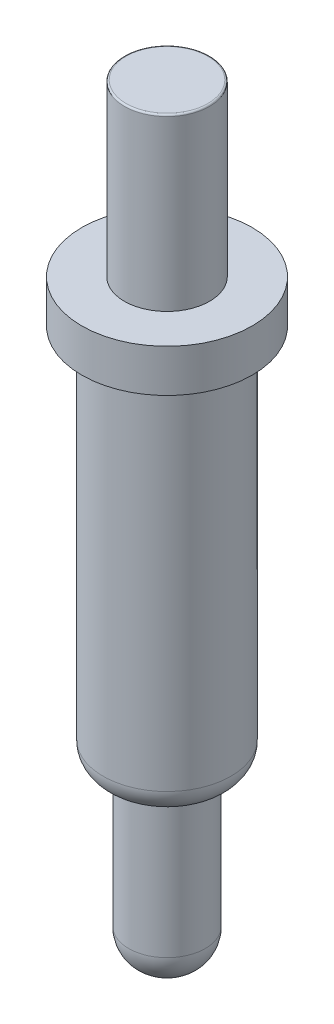
SolidWorks part; units mm, degrees
ref_plane "Front Plane" through (0, 0, 0) normal (0, 0, 1) x (1, 0, 0)
ref_plane "Top Plane" through (0, 0, 0) normal (0, 1, 0) x (1, 0, 0)
ref_plane "Right Plane" through (0, 0, 0) normal (1, 0, 0) x (0, 0, -1)
sketch "Sketch1" plane through (0, 0, 0) normal (0, 1, 0) x (1, 0, 0)
  circle A0 centre (0, 0) radius 1
  dimension "D1" = 2
extrude "Boss-Extrude1" add sketch "Sketch1" along normal blind 0.5
sketch "Sketch2" plane through (0, 0.5, 0) normal (0, 1, 0) x (1, 0, 0)
  circle A0 centre (0, 0) radius 0.5
  dimension "D1" = 1
extrude "Boss-Extrude2" add sketch "Sketch2" along normal blind 2
sketch "Sketch3" plane through (0, 0, 0) normal (0, -1, 0) x (1, 0, 0)
  circle A0 centre (0, 0) radius 0.75
  dimension "D1" = 1.5
extrude "Boss-Extrude3" add sketch "Sketch3" along normal blind 4.5
sketch "Sketch4" plane through (0, -4.5, 0) normal (0, -1, 0) x (1, 0, 0)
  circle A0 centre (0, 0) radius 0.45
  dimension "D1" = 0.9
extrude "Boss-Extrude4" add sketch "Sketch4" along normal blind 2
fillet "Fillet1" radius 0.02 1 edges at (0, 2.5, 0.5)
fillet "Fillet2" radius 0.3 1 edges at (0, -4.5, -0.75)
fillet "Fillet3" radius 0.4 1 edges at (0, -6.5, -0.45)
